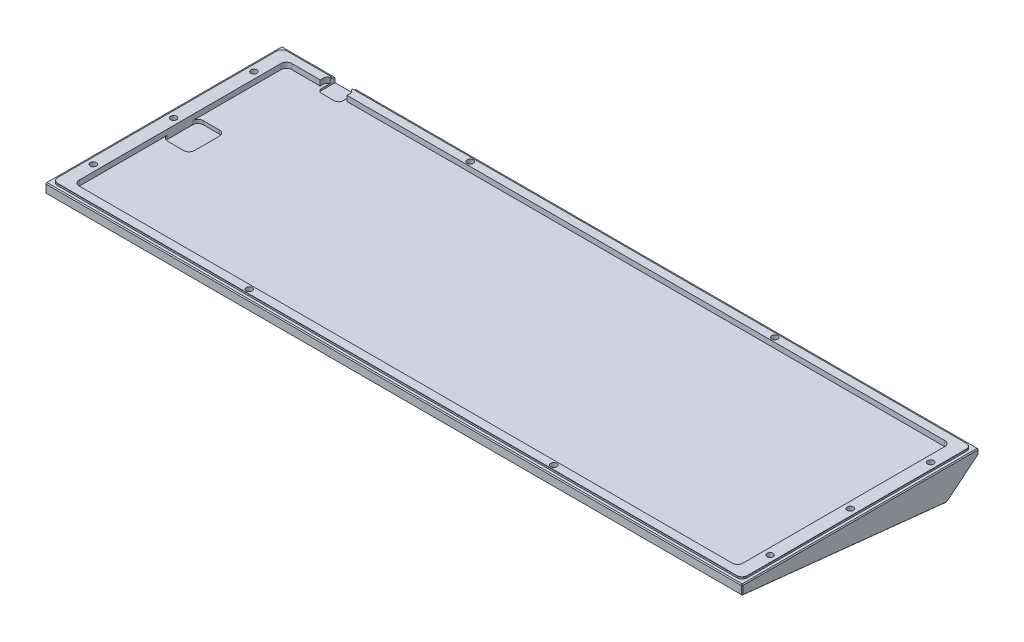
SolidWorks part; units mm, degrees
material "6061-T6 (SS)"
ref_plane "Front Plane" through (0, 0, 0) normal (0, 0, 1) x (1, 0, 0)
ref_plane "Top Plane" through (0, 0, 0) normal (0, 1, 0) x (1, 0, 0)
ref_plane "Right Plane" through (0, 0, 0) normal (1, 0, 0) x (0, 0, -1)
sketch "Sketch1" plane through (0, 0, 0) normal (0, 1, 0) x (1, 0, 0)
  line L1 (0, 0) -> (390.7, 0)
  line L2 (0, 0) -> (0, 132.7)
  line L3 (0, 132.7) -> (390.7, 132.7)
  line L4 (390.7, 0) -> (390.7, 132.7)
  dimension "D1" = 390.7
  dimension "D2" = 132.7
extrude "MainBody" add sketch "Sketch1" along normal blind 18.5
sketch "Sketch2" plane through (0, 18.5, 0) normal (0, 1, 0) x (1, 0, 0)
  line L0 (390.7, 132.7) -> (0, 132.7) construction
  line L1 (2, 130.7) -> (388.7, 130.7)
  line L2 (2, 130.7) -> (2, 2)
  line L3 (2, 2) -> (388.7, 2)
  line L4 (388.7, 130.7) -> (388.7, 2)
  line L5 (0, 132.7) -> (0, 0) construction
  line L7 (0, 132.7) -> (390.7, 132.7)
  line L8 (0, 132.7) -> (0, 0)
  line L9 (0, 0) -> (390.7, 0)
  line L10 (390.7, 132.7) -> (390.7, 0)
  point P4 (195.35, 130.7)
  point P7 (195.35, 132.7)
  point P8 (2, 66.35)
  point P11 (0, 66.35)
  line M5 (0, 132.7) -> (0, 0)
  line M6 (0, 0) -> (390.7, 0)
  line M7 (390.7, 0) -> (390.7, 132.7)
  line M8 (390.7, 132.7) -> (0, 132.7)
  dimension "D1" = 2
  dimension "D2" = 2
extrude "AligmentLip" cut sketch "Sketch2" against normal blind 1 contours L1 L4 L3 L2 M8 M5 M6 M7 region at (195.35, 18.5, -132.2874)
sketch "Sketch3" plane through (0, 0, 0) normal (-1, 0, 0) x (0, 0, 1)
  line L0 (-132.7, 14.5) -> (-114.794, 0)
  line L1 (-132.7, 17.5) -> (-132.7, 0) construction
  line L2 (-132.7, 0) -> (0, 0) construction
  line L3 (-114.794, 0) -> (0, 12.0653)
  line L4 (0, 17.5) -> (0, 0) construction
  line L5 (-132.7, 17.5) -> (0, 17.5) construction
  line L7 (-132.7, 17.5) -> (0, 17.5)
  line L8 (-132.7, 17.5) -> (-132.7, 0)
  line L9 (-132.7, 0) -> (0, 0)
  line L10 (0, 17.5) -> (0, 0)
  line M4 (-132.7, 17.5) -> (-132.7, 0)
  line M5 (-132.7, 0) -> (0, 0)
  line M6 (0, 0) -> (0, 17.5)
  dimension "D1" = 6
  dimension "D2" = 135
  dimension "D3" = 3
extrude "TypingAngle" cut sketch "Sketch3" against normal through all contours L0 M4 M5 | L3 M5 M6 region at (0, 4.8333, -126.7313) region at (0, 4.0218, -38.2647)
sketch "Sketch4" plane through (0, 18.5, 0) normal (0, 1, 0) x (1, 0, 0)
  line L0 (2, 130.7) -> (388.7, 130.7) construction
  line L1 (9.35, 125.9) -> (381.35, 125.9)
  line L2 (9.35, 125.9) -> (9.35, 6.8)
  line L3 (9.35, 6.8) -> (381.35, 6.8)
  line L4 (381.35, 125.9) -> (381.35, 6.8)
  line L5 (2, 130.7) -> (2, 2) construction
  point P4 (195.35, 125.9)
  point P7 (195.35, 130.7)
  point P8 (9.35, 66.35)
  point P11 (2, 66.35)
  dimension "D1" = 372
  dimension "D2" = 119.1
extrude "PCBCutout" cut sketch "Sketch4" against normal blind 3
sketch "Sketch8" plane through (0, 18.5, 0) normal (0, 1, 0) x (1, 0, 0)
  line L0 (195.35, 132.7) -> (195.35, 0) construction
  line L1 (390.7, 132.7) -> (0, 132.7) construction
  line L2 (0, 0) -> (390.7, 0) construction
  line L3 (0, 66.35) -> (195.35, 66.35) construction
  line L4 (0, 132.7) -> (0, 0) construction
  line L5 (2, 130.7) -> (388.7, 130.7) construction
  line L6 (2, 2) -> (388.7, 2) construction
  line L7 (2, 130.7) -> (2, 2) construction
  point P11 (110, 128.3)
  point P12 (5.7, 111.35)
  point P13 (5.7, 66.35)
  point P14 (5.7, 21.35)
  point P16 (110, 4.4)
  point P27 (280.7, 4.4)
  point P28 (385, 21.35)
  point P29 (385, 66.35)
  point P30 (385, 111.35)
  point P31 (280.7, 128.3)
  dimension "D1" = 2.4
  dimension "D2" = 2.4
  dimension "D3" = 110
  dimension "D4" = 45
  dimension "D5" = 45
  dimension "D6" = 3.7
hole_wizard "M3 Clearance Hole1" positions "3DSketch7" profile "Sketch10" hole size "M3" standard "ANSI Metric" end condition through all
sketch3d "3DSketch7"
  point P0 (110, 18.5, -128.3)
  point P3 (5.7, 18.5, -111.35)
  point P6 (5.7, 18.5, -66.35)
  point P9 (5.7, 18.5, -21.35)
  point P12 (110, 18.5, -4.4)
  point P15 (280.7, 18.5, -128.3)
  point P18 (280.7, 18.5, -4.4)
  point P21 (385, 18.5, -21.35)
  point P24 (385, 18.5, -66.35)
  point P27 (385, 18.5, -111.35)
sketch "Sketch10" plane through (110, 18.5, -128.3) normal (1, 0, 0) x (0, 0, 1)
  line L0 (0, 0) -> (0, 18.5)
  line L1 (0, 18.5) -> (1.7, 18.5)
  line L2 (1.7, 18.5) -> (1.7, 0)
  line L5 (1.7, 0) -> (0, 0)
  line L11 (0, -6.35) -> (0, 107.95) construction
  dimension "Thru Hole Dia." = 3.4
  dimension "Thru Hole Depth" = 18.5
sketch "Sketch11" plane through (0, 15.5, 0) normal (0, 1, 0) x (1, 0, 0)
  line L0 (195.35, 132.7) -> (195.35, 0) construction
  line L1 (0, 0) -> (390.7, 0) construction
  circle A0 centre (110, 128.3) radius 3.25
  circle A1 centre (5.7, 111.35) radius 3.25
  circle A2 centre (5.7, 66.35) radius 3.25
  circle A3 centre (5.7, 21.35) radius 3.25
  circle A4 centre (110, 4.4) radius 3.25
  circle A5 centre (280.7, 4.4) radius 3.25
  circle A6 centre (385, 21.35) radius 3.25
  circle A7 centre (385, 66.35) radius 3.25
  circle A8 centre (385, 111.35) radius 3.25
  circle A9 centre (280.7, 128.3) radius 3.25
  dimension "D1" = 6.5
extrude "Cut-Extrude2" cut sketch "Sketch11" against normal through all from offset 1 offset against normal yes
sketch "Sketch13" plane through (0, 15.5, 0) normal (0, 1, 0) x (1, 0, 0)
  line L0 (9.35, 125.9) -> (9.35, 6.8) construction
  line L1 (9.35, 76.35) -> (24.35, 76.35)
  line L2 (9.35, 76.35) -> (9.35, 56.35)
  line L3 (9.35, 56.35) -> (24.35, 56.35)
  line L4 (24.35, 76.35) -> (24.35, 56.35)
  line L5 (2, 130.7) -> (2, 2) construction
  point P6 (9.35, 66.35)
  point P9 (2, 66.35)
  dimension "D1" = 15
  dimension "D2" = 20
extrude "Cut-Extrude4" cut sketch "Sketch13" against normal blind 2
fillet "Fillet2" radius 3 12 edges at (381.35, 17, -125.9) (388.7, 18, -130.7) (388.7, 18, -2) (381.35, 17, -6.8) (9.35, 17, -6.8) (2, 18, -2) (9.35, 17, -125.9) (2, 18, -130.7) (9.35, 14.5, -56.35) (24.35, 14.5, -56.35) (9.35, 14.5, -76.35) (24.35, 14.5, -76.35)
chamfer "Chamfer1" distance 0.5 angle 45 13 edges at (195.35, 12.0653, 0) (390.7, 16, -132.7) (0, 16, -132.7) (0, 7.25, -123.747) (390.7, 7.25, -123.747) (390.7, 6.0327, -57.397) (390.7, 14.7827, 0) (0, 6.0327, -57.397) (0, 14.7827, 0) (0, 17.5, -66.35) (195.35, 17.5, 0) (390.7, 17.5, -66.35) (195.35, 17.5, -132.7) first distance on face at (195.35, 14.7827, 0) first distance on face at (195.35, 16, -132.7) first distance on face at (280.7, 13.5687, -131.55) first distance on face at (385, 0.7036, -108.1) first distance on face at (0, 12.3131, -76.0388) first distance on face at (390.7, 12.3131, -76.0388)
chamfer "Chamfer2" distance 0.1 angle 45 8 edges at (388.7, 18.5, -66.35) (387.8213, 18.5, -129.8213) (387.8213, 18.5, -2.8787) (195.35, 18.5, -130.7) (195.35, 18.5, -2) (2.8787, 18.5, -129.8213) (2.8787, 18.5, -2.8787) (2, 18.5, -66.35)
sketch "Sketch17" plane through (0, 11.9335, -1.2543) normal (0, -0.9945, 0.1045) x (1, 0, 0)
  line L0 (198.1, -60.7388) -> (196.1, -60.7388) construction
  line L1 (198.1, -68.7388) -> (196.1, -68.7388)
  line L2 (198.1, -68.7388) -> (198.1, -52.7388)
  line L3 (198.1, -52.7388) -> (196.1, -52.7388)
  line L4 (196.1, -68.7388) -> (196.1, -52.7388)
  line L5 (202.6, -61.2388) -> (200.6, -61.2388)
  line L6 (202.6, -61.2388) -> (202.6, -48.7388)
  line L7 (202.6, -48.7388) -> (200.6, -48.7388)
  line L8 (200.6, -61.2388) -> (200.6, -48.7388)
  line L9 (193.6, -61.2388) -> (191.6, -61.2388)
  line L10 (193.6, -61.2388) -> (193.6, -53.2388)
  line L11 (193.6, -53.2388) -> (191.6, -53.2388)
  line L12 (191.6, -61.2388) -> (191.6, -53.2388)
  line L13 (190.1, -61.2388) -> (188.1, -61.2388)
  line L14 (190.1, -61.2388) -> (190.1, -53.2388)
  line L15 (190.1, -53.2388) -> (188.1, -53.2388)
  line L16 (188.1, -61.2388) -> (188.1, -53.2388)
  line L17 (186.6, -61.2388) -> (184.6, -61.2388)
  line L18 (186.6, -61.2388) -> (186.6, -53.2388)
  line L19 (186.6, -53.2388) -> (184.6, -53.2388)
  line L20 (184.6, -61.2388) -> (184.6, -53.2388)
  line L25 (202.6, -61.2388) -> (188.1, -61.2388) construction
  line L26 (390.2, -114.1651) -> (0.5, -114.1651) construction
  line L27 (194.1, -64.7388) -> (198.1, -64.7388)
  line L28 (194.1, -62.7388) -> (198.1, -62.7388)
  line L29 (390.7, 1.2612) -> (0, 1.2612) construction
  line L31 (206.1, -53.2388) -> (204.1, -53.2388)
  line L32 (206.1, -53.2388) -> (206.1, -48.7388)
  line L33 (206.1, -48.7388) -> (204.1, -48.7388)
  line L34 (204.1, -53.2388) -> (204.1, -48.7388)
  circle A0 centre (201.6, -63.7388) radius 1
  circle A2 centre (194.1, -63.7388) radius 1
  circle A3 centre (197.1, -67.7388) radius 1
  circle A4 centre (197.1, -53.7388) radius 1
  circle A5 centre (201.6, -60.2388) radius 1
  circle A6 centre (201.6, -49.7388) radius 1
  circle A7 centre (205.1, -52.2388) radius 1
  circle A8 centre (205.1, -49.7388) radius 1
  circle A9 centre (192.6, -60.2388) radius 1
  circle A10 centre (192.6, -54.2388) radius 1
  circle A11 centre (189.1, -60.2388) radius 1
  circle A12 centre (189.1, -54.2388) radius 1
  circle A13 centre (185.6, -60.2388) radius 1
  circle A14 centre (185.6, -54.2388) radius 1
  point P28 (195.35, -61.2388)
  point P29 (201.6, -61.2388)
  point P33 (195.35, -114.1651)
  point P44 (197.1, -68.7388)
  dimension "D12" = 2
  dimension "D13" = 12.5
  dimension "D16" = 2
  dimension "D1" = 16
  dimension "D2" = 2
  dimension "D3" = 0
  dimension "D4" = 2.5
  dimension "D5" = 2.5
  dimension "D6" = 1.5
  dimension "D7" = 1.5
  dimension "D8" = 8
  dimension "D9" = 0.5
  dimension "D10" = 1.5
  dimension "D11" = 2.5
  dimension "D14" = 4.5
  dimension "D15" = 50
  dimension "D17" = 2
  dimension "D18" = 3
  dimension "D19" = 11
extrude "Cut-Extrude5" cut sketch "Sketch17" against normal blind 1 contours A7 | A8 L34 A7 L32 | A8 | A6 | A6 L8 A5 L6 | A5 | A4 | A4 L4 L28 L2 | L28 L4 L27 L2 | A3 L2 L27 L4 | A3 | A2 L27 L4 L28 | A2 | A0 | A9 | A10 L12 A9 L10 | A10 | A12 L16 A11 L14 | A11 | A12 | A14 | A14 L20 A13 L18 | A13 region at (197.1, 4.8529, -68.622) region at (197.1, 5.0495, -66.7509) region at (197.1, 5.271, -64.6439) region at (195.4722, 5.271, -64.6439) region at (197.1, 5.8052, -59.5616) region at (194.1, 5.271, -64.6439) region at (197.1, 6.3163, -54.6987) region at (201.6, 5.6368, -61.1631) region at (201.6, 6.1856, -55.9419) region at (201.6, 6.7344, -50.7206) region at (192.6, 5.6368, -61.1631) region at (192.6, 5.9504, -58.1795) region at (192.6, 6.264, -55.196) region at (189.1, 5.6368, -61.1631) region at (189.1, 5.9504, -58.1795) region at (189.1, 6.264, -55.196) region at (185.6, 5.6368, -61.1631) region at (185.6, 5.9504, -58.1795) region at (185.6, 6.264, -55.196) region at (205.1, 6.4731, -53.2069) region at (205.1, 6.6037, -51.9638) region at (205.1, 6.7344, -50.7206) region at (201.6, 5.271, -64.6439)
sketch "Sketch18" plane through (0, 0, -132.7) normal (0, 0, -1) x (-1, 0, 0)
  line L0 (-385.7, 18.5) -> (-5, 18.5) construction
  line L1 (-41.8, 18.5) -> (-29.8, 18.5)
  line L2 (-41.8, 18.5) -> (-41.8, 14.5)
  line L3 (-41.8, 14.5) -> (-29.8, 14.5)
  line L4 (-29.8, 18.5) -> (-29.8, 14.5)
  line L6 (-390.2, 14.5) -> (-0.5, 14.5) construction
  line L7 (0, 17) -> (0, 14.7385) construction
  point P6 (-35.8, 18.5)
  dimension "D1" = 35.8
  dimension "D3" = 12
extrude "Cut-Extrude6" cut sketch "Sketch18" against normal blind 10
sketch "Sketch12" plane through (0, 18.5, 0) normal (0, 1, 0) x (1, 0, 0)
  line L0 (381.35, 125.9) -> (9.35, 125.9) construction
  line L1 (28.3, 125.9) -> (43.3, 125.9)
  line L2 (28.3, 125.9) -> (28.3, 129.85)
  line L3 (28.3, 129.85) -> (43.3, 129.85)
  line L4 (43.3, 125.9) -> (43.3, 129.85)
  line L6 (390.7, 132.7) -> (0, 132.7) construction
  line L7 (41.8, 132.7) -> (29.8, 132.7) construction
  point P6 (35.8, 129.85)
  point P11 (35.8, 132.7)
  dimension "D1" = 15
  dimension "D2" = 2.85
extrude "Cut-Extrude3" cut sketch "Sketch12" against normal up to surface (3 mm away) up to face at (92.04, 15.5, -77.94)
fillet "Fillet1" radius 2.5 4 edges at (43.3, 17, -129.85) (28.3, 17, -129.85) (41.8, 15, -122.7) (29.8, 15, -122.7)
